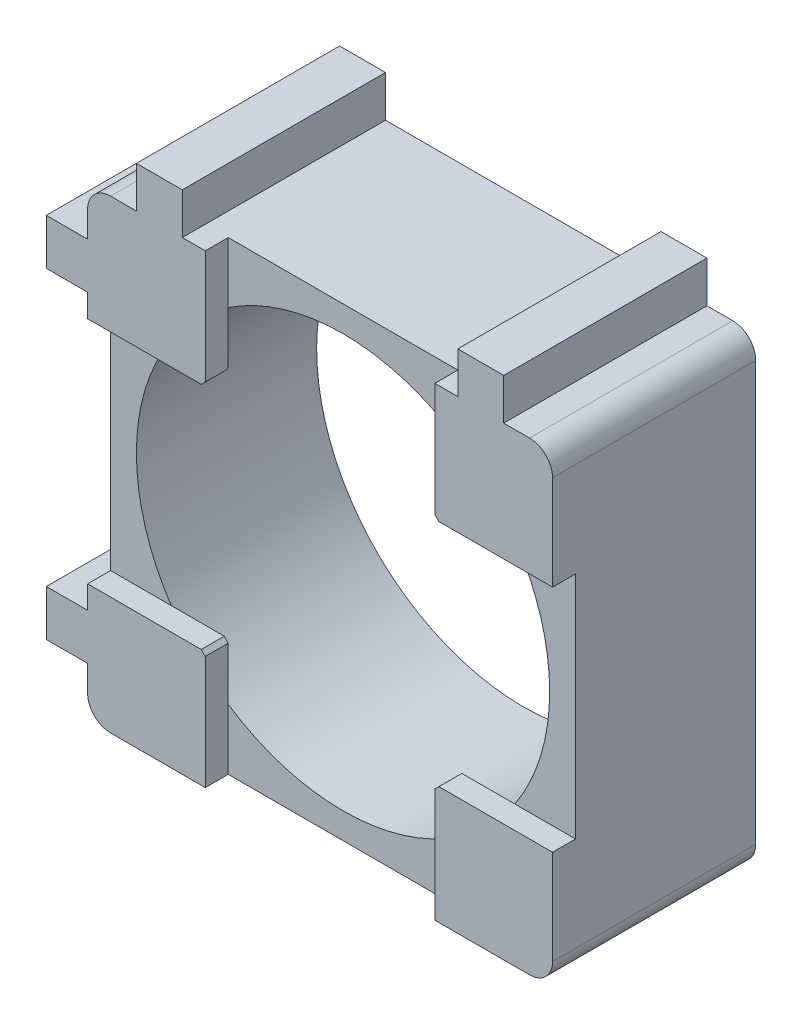
SolidWorks part; units mm, degrees
ref_plane "Top Plane" through (0, 0, 0) normal (0, 0, 1) x (1, 0, 0)
ref_plane "Right Plane" through (0, 0, 0) normal (0, 1, 0) x (1, 0, 0)
ref_plane "Front Plane" through (0, 0, 0) normal (1, 0, 0) x (0, 0, -1)
sketch "Sketch1" plane through (0, 0, 0) normal (0, 0, 1) x (1, 0, 0)
  line L0 (-10.125, 10.125) -> (10.125, -10.125) construction
  line L1 (-10.125, 10.125) -> (10.125, 10.125)
  line L2 (-10.125, 10.125) -> (-10.125, -10.125)
  line L3 (-10.125, -10.125) -> (10.125, -10.125)
  line L4 (10.125, 10.125) -> (10.125, -10.125)
  circle A0 centre (0, 0) radius 9
  circle A1 centre (0, 0) radius 7.1953 construction
  dimension "D1" = 18
  dimension "D2" = 20.25
extrude "Boss-Extrude1" add sketch "Sketch1" along normal mid plane 8.85
sketch "Sketch2" plane through (0, 0, 4.425) normal (0, 0, 1) x (1, 0, 0)
  circle A0 centre (0, 0) radius 9 construction
  circle A1 centre (0, 0) radius 9
  circle A2 centre (0, 0) radius 7.1953 construction
  circle A3 centre (0, 0) radius 7.1953
extrude "Boss-Extrude2" add sketch "Sketch2" against normal blind 1
sketch "Sketch3" plane through (0, 0, 4.425) normal (0, 0, 1) x (1, 0, 0)
  line L0 (-10.125, -5) -> (-5.1743, -5)
  line L1 (-10.125, 0) -> (-7.1953, 0) construction
  line L2 (-10.125, 5) -> (-5.1743, 5)
  line L3 (-5, 10.125) -> (-5, 5.1743)
  line L4 (-10.125, 10.125) -> (-10.125, -10.125)
  line L5 (-10.125, -10.125) -> (10.125, -10.125)
  line L6 (10.125, -10.125) -> (10.125, 10.125)
  line L7 (10.125, 10.125) -> (-10.125, 10.125)
  line L8 (-10.125, 5) -> (-10.125, -5)
  line L9 (-5, -10.125) -> (5, -10.125)
  line L10 (10.125, -5) -> (10.125, 5)
  line L11 (5, 10.125) -> (-5, 10.125)
  line L12 (5, 10.125) -> (5, 5.1743)
  line L13 (10.125, 5) -> (5.1743, 5)
  line L14 (10.125, -5) -> (5.1743, -5)
  line L15 (5, -10.125) -> (5, -5.1743)
  line L16 (-5, -10.125) -> (-5, -5.1743)
  line L17 (7.1953, 0) -> (10.125, 0) construction
  circle A0 centre (0, 0) radius 7.1953 construction
  arc A1 (-5, 5.1743) -> (-5.1743, 5) centre (0, 0) ccw
  arc A2 (-5.1743, -5) -> (-5, -5.1743) centre (0, 0) ccw
  arc A3 (5, -5.1743) -> (5.1743, -5) centre (0, 0) ccw
  arc A4 (5.1743, 5) -> (5, 5.1743) centre (0, 0) ccw
  point P28 (0, 0)
  dimension "D2" = 10
  dimension "D1" = 0
  dimension "D3" = 4
extrude "Cut-Extrude1" cut sketch "Sketch3" against normal blind 1
fillet "Fillet1" radius 1 4 edges at (-10.125, 10.125, 0) (-10.125, -10.125, 0) (10.125, 10.125, 0) (10.125, -10.125, 0)
sketch "Sketch4" plane through (-10.125, 0, 0) normal (-1, 0, 0) x (0, 0, 1)
  line L0 (-4.425, 9.125) -> (-4.425, -9.125) construction
  line L1 (-4.425, 8) -> (4.425, 8)
  line L2 (-4.425, 8) -> (-4.425, 6)
  line L3 (-4.425, 6) -> (4.425, 6)
  line L4 (4.425, 8) -> (4.425, 6)
  line L5 (4.425, 9.125) -> (4.425, 5) construction
  line L6 (-8.041, 0) -> (10.4895, 0) construction
  line L7 (4.425, -8) -> (4.425, -6)
  line L8 (-4.425, -6) -> (4.425, -6)
  line L9 (-4.425, -8) -> (-4.425, -6)
  line L10 (-4.425, -8) -> (4.425, -8)
  dimension "D1" = 12
  dimension "D2" = 2
extrude "Boss-Extrude3" add sketch "Sketch4" along normal blind 1.8
pattern_circular "CirPattern1" count 2 every 90 about axis through (0, 0, 4.425) along (0, 0, -1) of "Boss-Extrude3"
